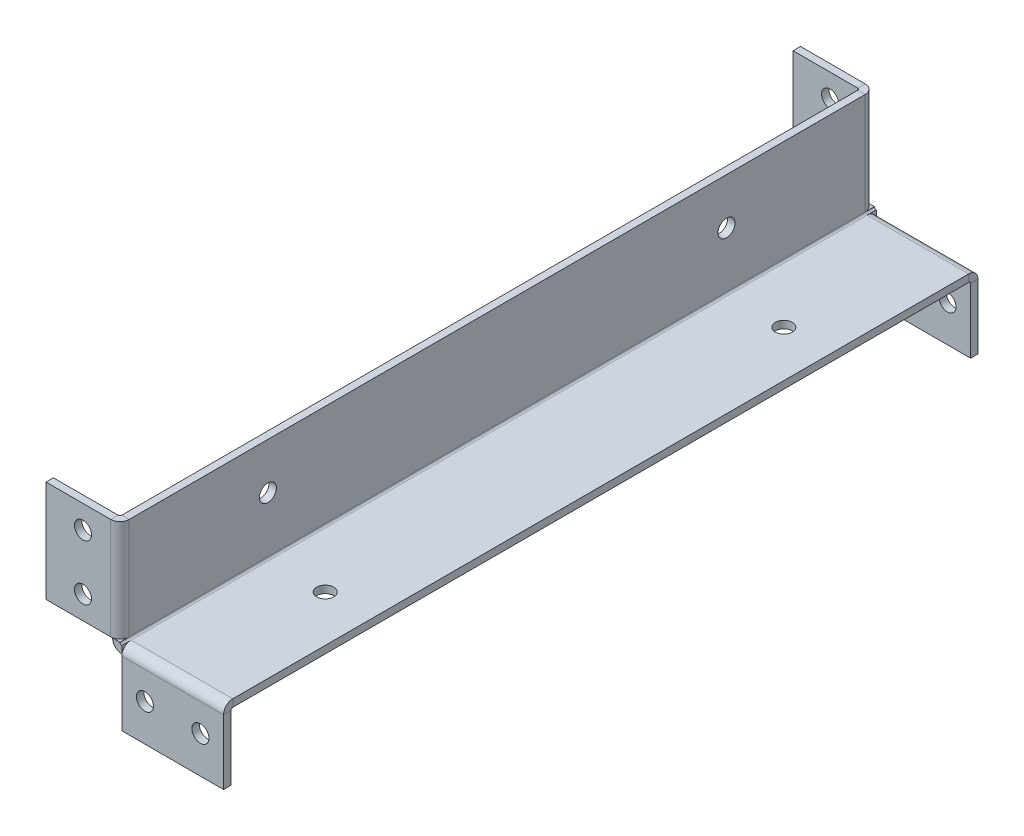
SolidWorks part; units mm, degrees
note: The reader was unsure of these and kept them because the rebuilt part matched: flange length of "Edge-Flange1", "Edge-Flange2".
ref_plane "Front Plane" through (0, 0, 0) normal (0, 0, 1) x (1, 0, 0)
ref_plane "Top Plane" through (0, 0, 0) normal (0, 1, 0) x (1, 0, 0)
ref_plane "Right Plane" through (0, 0, 0) normal (1, 0, 0) x (0, 0, -1)
sketch "Sketch1" plane through (0, 0, 0) normal (0, 1, 0) x (1, 0, 0)
  line L1 (30, 204) -> (-30, 204)
  line L2 (30, 204) -> (30, -204)
  line L3 (30, -204) -> (-30, -204)
  line L4 (-30, 204) -> (-30, -204)
  line L5 (30, 204) -> (-30, -204) construction
  line L6 (30, -204) -> (-30, 204) construction
  point P0 (0, 0)
  dimension "D1" = 60
  dimension "D2" = 408
sheet metal parameters "Sheet-Metal1" thickness 4 parameters "D1"=1
base flange "Base-Flange1" sketch "Sketch1" thickness 4 reverse thickness direction yes parameters "D1"=1
edge flange "Edge-Flange1" sketch "Sketch5" flange angle 90 flange length 60 flange position material inside bend radius 1 thickness 4 parameters "D6"=10
sketch "Sketch5" plane through (-30, 4, 0) normal (-1, 0, 0) x (0, 0, 1)
  line L2 (-204, 0) -> (-204, 56)
  line L3 (-204, 56) -> (204, 56)
  line L4 (204, 56) -> (204, 0)
  line L5 (-204, 0) -> (204, 0) construction
  line L6 (-204, 0) -> (204, 0)
bend "EdgeBend1" bend radius 1 bend angle 90 parameters "D5"=1
edge flange "Edge-Flange2" sketch "Sketch14" flange profiles "Sketch14", "Sketch15", "Sketch16", "Sketch17" flange angle 90 flange length 40 flange position material inside bend radius 1 thickness 4 relief none parameters "D6"=10, "D8"=0.5
sketch "Sketch14" plane through (-30, 0, 204) normal (0, 0, -1) x (0, -1, 0)
  line L1 (-5, 0) -> (-60, 0) construction
  line L2 (-60, 0) -> (-60, 36)
  line L3 (-60, 36) -> (-5, 36)
  line L4 (-5, 36) -> (-5, 0)
  line L5 (-5, 0) -> (-60, 0)
sketch "Sketch15" plane through (0, 0, 204) normal (0, 0, -1) x (1, 0, 0)
  line L0 (30, 0) -> (-25, 0) construction
  line L1 (30, 0) -> (-25, 0)
  line L2 (30, 0) -> (30, 36)
  line L3 (30, 36) -> (-25, 36)
  line L4 (-25, 36) -> (-25, 0)
sketch "Sketch16" plane through (-30, 0, -204) normal (0, 0, 1) x (0, 1, 0)
  line L0 (60, 0) -> (5, 0) construction
  line L1 (60, 0) -> (5, 0)
  line L2 (60, 0) -> (60, 36)
  line L3 (60, 36) -> (5, 36)
  line L4 (5, 36) -> (5, 0)
sketch "Sketch17" plane through (0, 0, -204) normal (0, 0, 1) x (-1, 0, 0)
  line L0 (25, 0) -> (-30, 0) construction
  line L1 (25, 0) -> (-30, 0)
  line L2 (25, 0) -> (25, 36)
  line L3 (25, 36) -> (-30, 36)
  line L4 (-30, 36) -> (-30, 0)
bend "EdgeBend2" bend radius 1 bend angle 90 parameters "D5"=2
bend "EdgeBend3" bend radius 1 bend angle 90 parameters "D5"=3
bend "EdgeBend4" bend radius 1 bend angle 90 parameters "D5"=4
bend "EdgeBend5" bend radius 1 bend angle 90 parameters "D5"=5
sketch "Sketch18" plane through (0, 0, 204) normal (0, 0, 1) x (1, 0, 0)
  line L0 (-25, 4) -> (30, 4) construction
  line L1 (-26, 60) -> (-26, 5) construction
  line L2 (-66, 60) -> (-31, 60) construction
  line L3 (30, -1) -> (30, -36) construction
  circle A0 centre (-46, 47.5) radius 4.6
  circle A1 centre (-46, 17.5) radius 4.6
  circle A2 centre (-12.5, -16) radius 4.6
  circle A3 centre (17.5, -16) radius 4.6
  dimension "D7" = 9.2
  dimension "D1" = 30
  dimension "D2" = 30
  dimension "D3" = 20
  dimension "D4" = 20
  dimension "D5" = 12.5
  dimension "D6" = 12.5
extrude "Extrude1" cut sketch "Sketch18" against normal through all normal cut yes
sketch "Sketch19" plane through (-26, 0, 0) normal (1, 0, 0) x (0, 0, -1)
  line L0 (-199, 60) -> (199, 60) construction
  line L1 (-204, 5) -> (-204, 60) construction
  line L2 (204, 5) -> (204, 60) construction
  circle A0 centre (-124, 35) radius 4.6
  circle A1 centre (124, 35) radius 4.6
  dimension "D4" = 9.2
  dimension "D1" = 25
  dimension "D2" = 80
  dimension "D3" = 80
extrude "Extrude2" cut sketch "Sketch19" against normal blind 4 normal cut yes
sketch "Sketch20" plane through (0, 4, 0) normal (0, 1, 0) x (1, 0, 0)
  line L0 (30, -199) -> (30, 199) construction
  line L1 (-25, -204) -> (30, -204) construction
  line L2 (30, 204) -> (-25, 204) construction
  circle A0 centre (5, 124) radius 4.6
  circle A1 centre (5, -124) radius 4.6
  dimension "D2" = 9.2
  dimension "D1" = 25
  dimension "D3" = 80
  dimension "D4" = 80
extrude "Extrude3" cut sketch "Sketch20" against normal blind 4 normal cut yes
flat pattern "Flat-Pattern1" [suppressed]
sketch "Bend-Lines1" plane through (0, 4, 0) normal (0, 1, 0) x (-1, 0, 0)
  line L0 (25, -199.4012) -> (-30, -199.4012) construction
  line L1 (82.8023, -199.4012) -> (27.8023, -199.4012) construction
  line L2 (-30, 199.4012) -> (25, 199.4012) construction
  line L3 (27.8023, 199.4012) -> (82.8023, 199.4012) construction
  line L4 (26.4012, -203) -> (26.4012, 203) construction
  line L5 (25, -199.4012) -> (-30, -199.4012) construction
  line L6 (82.8023, -199.4012) -> (27.8023, -199.4012) construction
  line L7 (-30, 199.4012) -> (25, 199.4012) construction
  line L8 (27.8023, 199.4012) -> (82.8023, 199.4012) construction
  line L9 (26.4012, -203) -> (26.4012, 203) construction
sketch3d "Bounding-Box1" [suppressed]
  line L0 (52.8023, 32.8023, 0) -> (52.8023, -438.8023, 0) construction
  line L1 (-60, 32.8023, 0) -> (-60, -438.8023, 0) construction
  line L2 (52.8023, 32.8023, 0) -> (-60, 32.8023, 0) construction
  line L3 (52.8023, -438.8023, 0) -> (-60, -438.8023, 0) construction
bend of the flat pattern "Flatten-<EdgeBend1>1"
bend of the flat pattern "Flatten-<EdgeBend2>1"
bend of the flat pattern "Flatten-<EdgeBend3>1"
bend of the flat pattern "Flatten-<EdgeBend4>1"
bend of the flat pattern "Flatten-<EdgeBend5>1"
